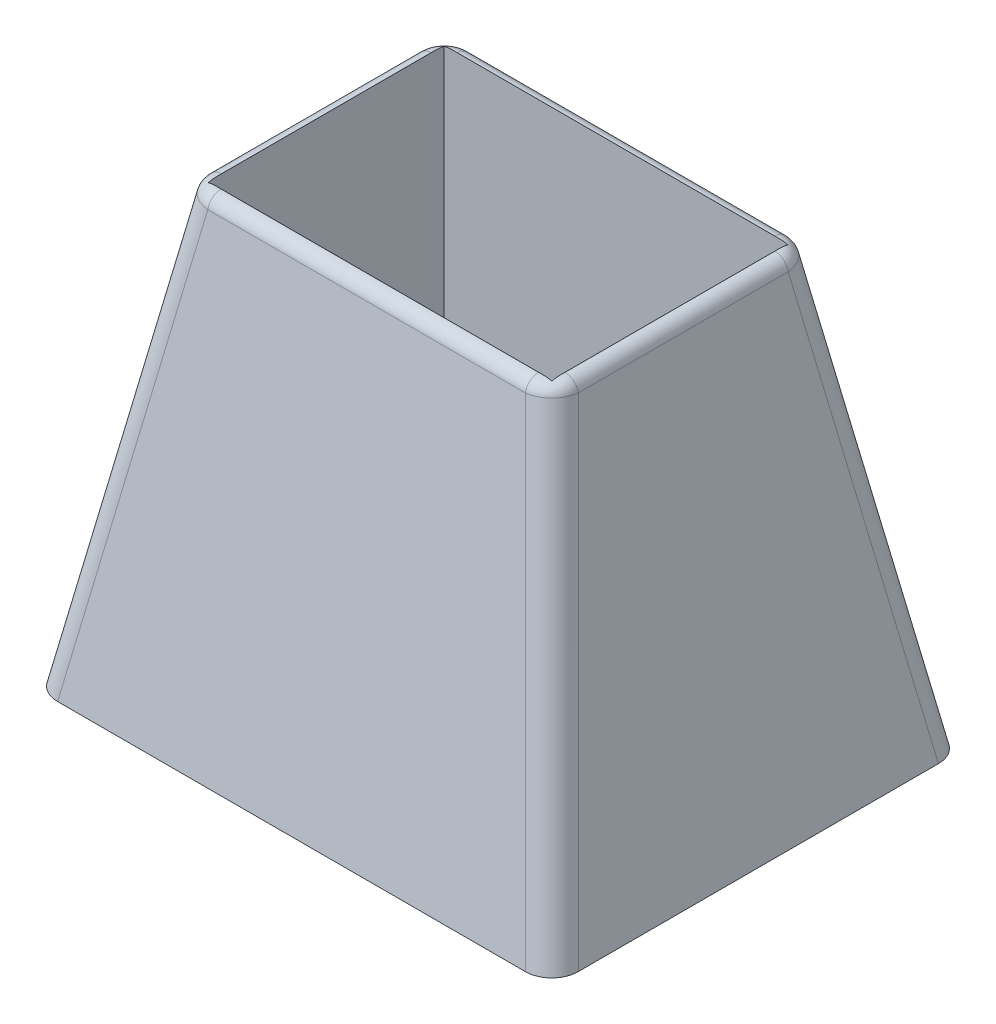
SolidWorks part; units mm, degrees
ref_plane "Front Plane" through (0, 0, 0) normal (0, 0, 1) x (1, 0, 0)
ref_plane "Top Plane" through (0, 0, 0) normal (0, 1, 0) x (1, 0, 0)
ref_plane "Right Plane" through (0, 0, 0) normal (1, 0, 0) x (0, 0, -1)
sketch "Sketch1" plane through (0, 0, 0) normal (0, 1, 0) x (1, 0, 0)
  line L1 (0, 0) -> (54.5, 0)
  line L2 (0, 0) -> (0, -38.5)
  line L3 (0, -38.5) -> (54.5, -38.5)
  line L4 (54.5, 0) -> (54.5, -38.5)
  dimension "D1" = 54.5
  dimension "D2" = 38.5
extrude "Boss-Extrude1" add sketch "Sketch1" against normal blind 65 draft 10 draft outward yes
sketch "Esboço3" plane through (0, 0, 0) normal (0, 1, 0) x (1, 0, 0)
  line L0 (0, -38.5) -> (54.5, -38.5) construction
  line L1 (1.7, -1.7) -> (52.8, -1.7)
  line L2 (1.7, -1.7) -> (1.7, -36.8)
  line L3 (1.7, -36.8) -> (52.8, -36.8)
  line L4 (52.8, -1.7) -> (52.8, -36.8)
  line L5 (54.5, -38.5) -> (54.5, 0) construction
  dimension "D1" = 51.1
  dimension "D2" = 35.1
  dimension "D3" = 1.7
  dimension "D4" = 1.7
extrude "Corte-extrusão1" cut sketch "Esboço3" against normal blind 60
fillet "Filete1" radius 4 4 edges at (60.2306, -32.5, 44.2306) (60.2306, -32.5, -5.7306) (-5.7306, -32.5, -5.7306) (-5.7306, -32.5, 44.2306)
fillet "Filete2" radius 2 8 edges at (1.1467, 0, 37.3533) (1.1467, 0, 1.1467) (53.3533, 0, 1.1467) (53.3533, 0, 37.3533) (54.5, 0, 19.25) (27.25, 0, 0) (0, 0, 19.25) (27.25, 0, 38.5)
